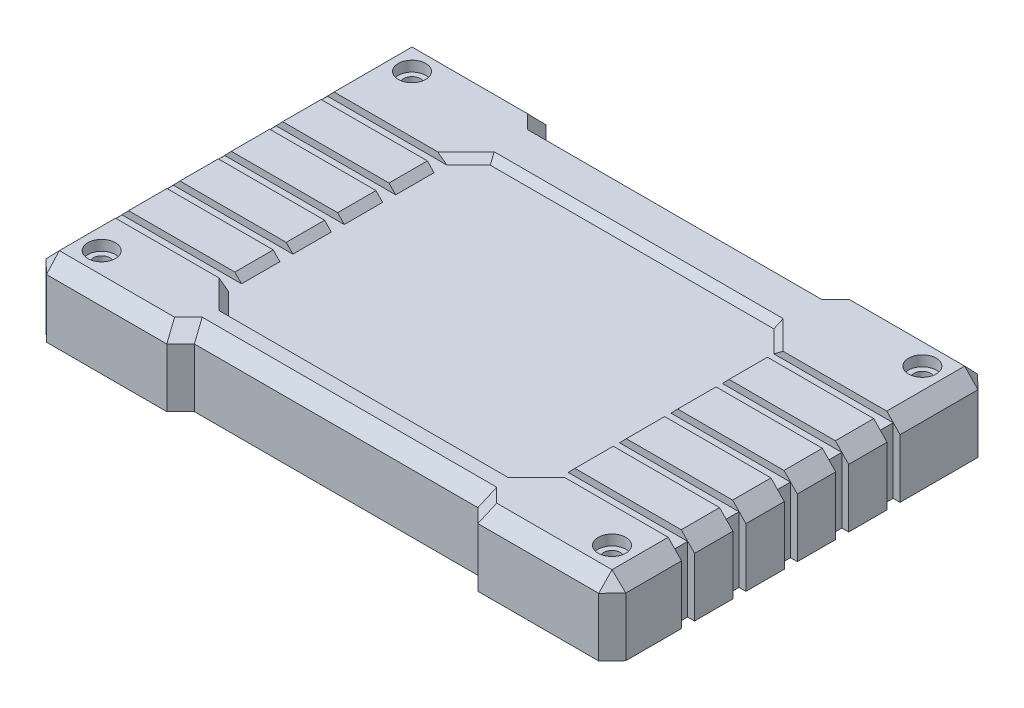
SolidWorks part; units mm, degrees
ref_plane "Спереди" through (0, 0, 0) normal (0, 0, 1) x (1, 0, 0)
ref_plane "Сверху" through (0, 0, 0) normal (0, 1, 0) x (1, 0, 0)
ref_plane "Справа" through (0, 0, 0) normal (1, 0, 0) x (0, 0, -1)
sketch "Эскиз1" plane through (0, 0, 0) normal (0, 1, 0) x (1, 0, 0)
  line L6 (-37, -22.5) -> (37, -22.5)
  line L9 (-37, -22.5) -> (-37, 22.5)
  line L14 (-37, 22.5) -> (37, 22.5)
  line L15 (37, -22.5) -> (37, 22.5)
  line L20 (-37, -22.5) -> (37, 22.5) construction
  line L21 (-37, 22.5) -> (37, -22.5) construction
  dimension "D1" = 74
  dimension "D2" = 45
extrude "Бобышка-Вытянуть1" add sketch "Эскиз1" along normal blind 2
sketch "Эскиз2" plane through (-37, 0, 0) normal (-1, 0, 0) x (0, 0, 1)
  line L0 (22.5, 2) -> (22.5, 0) construction
  line L1 (-22.5, 2) -> (22.5, 2)
  line L2 (-22.5, 2) -> (-22.5, -7.5)
  line L3 (-22.5, -7.5) -> (22.5, -7.5)
  line L4 (22.5, 2) -> (22.5, -7.5)
  dimension "D1" = 9.5
extrude "Бобышка-Вытянуть2" add sketch "Эскиз2" along normal blind 4
sketch "Эскиз3" plane through (37, 0, 0) normal (1, 0, 0) x (0, 0, -1)
  line L1 (-22.5, 2) -> (22.5, 2)
  line L2 (-22.5, 2) -> (-22.5, -7.5)
  line L3 (-22.5, -7.5) -> (22.5, -7.5)
  line L4 (22.5, 2) -> (22.5, -7.5)
extrude "Бобышка-Вытянуть3" add sketch "Эскиз3" along normal blind 4
sketch "Эскиз4" plane through (0, 0, -22.5) normal (0, 0, -1) x (-1, 0, 0)
  line L1 (-41, 2) -> (41, 2)
  line L2 (-41, 2) -> (-41, -7.5)
  line L3 (-41, -7.5) -> (41, -7.5)
  line L4 (41, 2) -> (41, -7.5)
extrude "Бобышка-Вытянуть4" add sketch "Эскиз4" along normal blind 3
sketch "Эскиз5" plane through (0, 0, 22.5) normal (0, 0, 1) x (1, 0, 0)
  line L1 (-41, 2) -> (41, 2)
  line L2 (-41, 2) -> (-41, -7.5)
  line L3 (-41, -7.5) -> (41, -7.5)
  line L4 (41, 2) -> (41, -7.5)
extrude "Бобышка-Вытянуть5" add sketch "Эскиз5" along normal blind 3
sketch "Эскиз13" plane through (0, 0, 0) normal (0, -1, 0) x (1, 0, 0)
  line L0 (0, 22.5) -> (0, 0) construction
  line L1 (-37, 22.5) -> (37, 22.5) construction
  line L2 (-37, 22.5) -> (-37, -22.5) construction
  line L3 (-37, -22.5) -> (37, -22.5) construction
  line L4 (37, 22.5) -> (37, -22.5) construction
  line L5 (0, -1.75) -> (0, 0) construction
  line L6 (-33, -18.5) -> (33, -18.5) construction
  line L7 (-33, -18.5) -> (-33, 15) construction
  line L8 (-33, 15) -> (33, 15) construction
  line L9 (33, -18.5) -> (33, 15) construction
  line L10 (-33, -18.5) -> (33, 15) construction
  line L11 (-33, 15) -> (33, -18.5) construction
  line L14 (-37, -19.5) -> (-37, -22.5)
  line L16 (-37, -22.5) -> (-34, -22.5)
  line L17 (-37, 22.5) -> (-34, 22.5)
  line L18 (-37, 22.5) -> (-37, 19.5)
  line L19 (37, -22.5) -> (34, -22.5)
  line L20 (37, -19.5) -> (37, -22.5)
  line L21 (37, 22.5) -> (34, 22.5)
  line L22 (37, 22.5) -> (37, 19.5)
  circle A0 centre (-33, -18.5) radius 1 construction
  circle A1 centre (-33, -18.5) radius 2 construction
  circle A2 centre (33, -18.5) radius 1 construction
  circle A3 centre (33, -18.5) radius 2 construction
  circle A4 centre (-33, 15) radius 1 construction
  circle A5 centre (-33, 15) radius 2 construction
  circle A6 centre (33, 15) radius 1 construction
  circle A7 centre (33, 15) radius 2 construction
  circle A10 centre (-37, -22.5) radius 1 construction
  circle A12 centre (-37, -22.5) radius 3 construction
  arc A13 (-37, -19.5) -> (-34, -22.5) centre (-37, -22.5) cw
  arc A15 (-34, 22.5) -> (-37, 19.5) centre (-37, 22.5) cw
  arc A16 (37, -19.5) -> (34, -22.5) centre (37, -22.5) ccw
  arc A17 (34, 22.5) -> (37, 19.5) centre (37, 22.5) ccw
  point P9 (0, -1.75)
  dimension "D4" = 2
  dimension "D5" = 4
  dimension "D6" = 6
  dimension "D7" = 2
  dimension "D8" = 1.75
  dimension "D1" = 4
  dimension "D2" = 33.5
  dimension "D3" = 66
extrude "Бобышка-Вытянуть11" add sketch "Эскиз13" along normal up to vertex (7.5 mm away) up to point (-37, -7.5, -22.5)
sketch "Эскиз15" plane through (0, -7.5, 0) normal (0, -1, 0) x (1, 0, 0)
  line L0 (-37, -19.5) -> (-37, -22.5) construction
  line L1 (-34, -22.5) -> (-37, -22.5) construction
  line L2 (-37, 19.5) -> (-37, 22.5) construction
  line L3 (-34, 22.5) -> (-37, 22.5) construction
  line L4 (0, 22.5) -> (0, -22.5) construction
  line L5 (-34, 22.5) -> (34, 22.5) construction
  line L6 (34, -22.5) -> (-34, -22.5) construction
  line L7 (34, -22.5) -> (37, -22.5) construction
  line L8 (37, -22.5) -> (37, -19.5) construction
  line L9 (34, 22.5) -> (37, 22.5) construction
  line L10 (37, 22.5) -> (37, 19.5) construction
  circle A0 centre (-37, -22.5) radius 1.2
  arc A1 (-37, 19.5) -> (-34, 22.5) centre (-37, 22.5) ccw construction
  circle A2 centre (-37, 22.5) radius 1.2
  circle A3 centre (37, -22.5) radius 1.2
  circle A4 centre (37, 22.5) radius 1.2
  dimension "D1" = 2.4
extrude "Вырез-Вытянуть1" cut sketch "Эскиз15" against normal through all
sketch "Эскиз16" plane through (0, 0, 0) normal (0, -1, 0) x (1, 0, 0)
  line L0 (-37, -5.5) -> (3, -5.5) construction
  line L1 (37, -19) -> (-37, -19) construction
  line L2 (37, -19) -> (37, 22.5) construction
  line L3 (37, 22.5) -> (-37, 22.5) construction
  line L4 (-37, -19) -> (-37, 22.5) construction
  line L5 (0, 1.75) -> (0, 3.5) construction
  line L6 (-33, -15) -> (33, -15) construction
  line L7 (-33, -15) -> (-33, 18.5) construction
  line L8 (-33, 18.5) -> (33, 18.5) construction
  line L9 (33, -15) -> (33, 18.5) construction
  line L10 (-33, -15) -> (33, 18.5) construction
  line L11 (-33, 18.5) -> (33, -15) construction
  line L12 (37, -19) -> (-37, 22.5) construction
  line L13 (37, 22.5) -> (-37, -19) construction
  line L14 (3, -5.5) -> (3, -19) construction
  line L15 (-37, 22.5) -> (-37, -5.5) construction
  line L16 (3, -19) -> (37, -19) construction
  line L18 (-34, 22.5) -> (34, 22.5) construction
  line L19 (-34, 22.5) -> (34, 22.5) construction
  line L20 (37, 19.5) -> (37, -19) construction
  circle A0 centre (-33, -15) radius 0.9 construction
  circle A1 centre (-33, -1.5) radius 0.9
  circle A2 centre (33, -15) radius 0.9
  circle A3 centre (7, -15) radius 0.9
  circle A4 centre (-33, 18.5) radius 0.9
  circle A5 centre (33, 18.5) radius 0.9
  arc A7 (34, 22.5) -> (37, 19.5) centre (37, 22.5) ccw construction
  arc A8 (34, 22.5) -> (37, 19.5) centre (37, 22.5) ccw construction
  circle A9 centre (-33, 18.5) radius 2
  circle A10 centre (33, 18.5) radius 2
  circle A11 centre (33, -15) radius 2
  circle A12 centre (7, -15) radius 2
  circle A13 centre (-33, -1.5) radius 2
  point P7 (0, 1.75)
  dimension "D9" = 1.8
  dimension "D10" = 4
  dimension "D11" = 26
  dimension "D1" = 33.5
  dimension "D2" = 66
  dimension "D3" = 1.75
  dimension "D4" = 74
  dimension "D5" = 41.5
  dimension "D6" = 28
  dimension "D7" = 40
  dimension "D8" = 20
extrude "Бобышка-Вытянуть12" add sketch "Эскиз16" along normal blind 4
sketch "Эскиз17" plane through (-41, 0, 0) normal (-1, 0, 0) x (0, 0, 1)
  line L0 (15.531, -7.5) -> (9.969, -7.5)
  line L1 (15.531, -7.5) -> (15.531, 2)
  line L2 (15.531, 2) -> (9.969, 2)
  line L3 (9.969, -7.5) -> (9.969, 2)
  line L4 (-14.269, -7.5) -> (-25.5, -7.5)
  line L5 (8.081, -7.5) -> (2.519, -7.5)
  line L6 (8.081, -7.5) -> (8.081, 2)
  line L7 (8.081, 2) -> (2.519, 2)
  line L8 (2.519, -7.5) -> (2.519, 2)
  line L9 (0.631, -7.5) -> (-4.931, -7.5)
  line L10 (0.631, -7.5) -> (0.631, 2)
  line L11 (0.631, 2) -> (-4.931, 2)
  line L12 (-4.931, -7.5) -> (-4.931, 2)
  line L13 (-6.819, -7.5) -> (-12.381, -7.5)
  line L14 (-6.819, -7.5) -> (-6.819, 2)
  line L15 (-6.819, 2) -> (-12.381, 2)
  line L16 (-12.381, -7.5) -> (-12.381, 2)
  line L17 (-14.269, -7.5) -> (-14.269, 2)
  line L18 (-25.5, -7.5) -> (-25.5, 2)
  line L19 (-14.269, 2) -> (-25.5, 2)
  line L20 (17.419, -7.5) -> (25.5, -7.5)
  line L21 (17.419, -7.5) -> (17.419, 2)
  line L22 (25.5, -7.5) -> (25.5, 2)
  line L23 (17.419, 2) -> (25.5, 2)
  line L24 (-14.269, -7.5) -> (-12.381, -7.5) construction
  line L25 (-6.819, -7.5) -> (-4.931, -7.5) construction
  line L26 (0.631, -7.5) -> (2.519, -7.5) construction
  line L27 (8.081, -7.5) -> (9.969, -7.5) construction
  line L28 (15.531, -7.5) -> (17.419, -7.5) construction
  line L29 (25.5, 2) -> (-25.5, 2) construction
  dimension "D1" = 8.081
  dimension "D2" = 11.231
  dimension "D3" = 5.562
  dimension "D4" = 1.888
extrude "Бобышка-Вытянуть13" add sketch "Эскиз17" along normal blind 1
sketch "Эскиз18" plane through (41, 0, 0) normal (1, 0, 0) x (0, 0, -1)
  line L0 (-15.531, 2) -> (-9.969, 2)
  line L1 (-15.531, 2) -> (-15.531, -7.5)
  line L2 (-15.531, -7.5) -> (-9.969, -7.5)
  line L3 (-9.969, 2) -> (-9.969, -7.5)
  line L4 (14.269, 2) -> (25.5, 2)
  line L5 (-8.081, 2) -> (-2.519, 2)
  line L6 (-8.081, 2) -> (-8.081, -7.5)
  line L7 (-8.081, -7.5) -> (-2.519, -7.5)
  line L8 (-2.519, 2) -> (-2.519, -7.5)
  line L9 (-0.631, 2) -> (4.931, 2)
  line L10 (-0.631, 2) -> (-0.631, -7.5)
  line L11 (-0.631, -7.5) -> (4.931, -7.5)
  line L12 (4.931, 2) -> (4.931, -7.5)
  line L13 (6.819, 2) -> (12.381, 2)
  line L14 (6.819, 2) -> (6.819, -7.5)
  line L15 (6.819, -7.5) -> (12.381, -7.5)
  line L16 (12.381, 2) -> (12.381, -7.5)
  line L17 (14.269, 2) -> (14.269, -7.5)
  line L18 (25.5, 2) -> (25.5, -7.5)
  line L19 (14.269, -7.5) -> (25.5, -7.5)
  line L20 (-17.419, 2) -> (-25.5, 2)
  line L21 (-17.419, 2) -> (-17.419, -7.5)
  line L22 (-25.5, 2) -> (-25.5, -7.5)
  line L23 (-17.419, -7.5) -> (-25.5, -7.5)
  line L24 (14.269, 2) -> (12.381, 2) construction
  line L25 (6.819, 2) -> (4.931, 2) construction
  line L26 (-0.631, 2) -> (-2.519, 2) construction
  line L27 (-8.081, 2) -> (-9.969, 2) construction
  line L28 (-15.531, 2) -> (-17.419, 2) construction
  line L30 (-25.5, -7.5) -> (25.5, -7.5) construction
  dimension "D1" = 8.081
  dimension "D2" = 11.231
  dimension "D3" = 5.562
  dimension "D4" = 1.888
extrude "Бобышка-Вытянуть14" add sketch "Эскиз18" along normal blind 1
sketch "Эскиз19" plane through (0, 2, 0) normal (0, 1, 0) x (1, 0, 0)
  line L0 (-42, 25.5) -> (-42, 27.5)
  line L1 (-42, -25.5) -> (-42, -27.5)
  line L2 (42, 25.5) -> (42, 27.5)
  line L3 (42, -25.5) -> (42, -27.5)
  line L4 (42, -27.5) -> (22.5537, -27.5)
  line L5 (-42, -27.5) -> (-22.5537, -27.5)
  line L6 (-42, 27.5) -> (-22.5537, 27.5)
  line L7 (42, 27.5) -> (22.5537, 27.5)
  line L8 (-22.5537, 17.6481) -> (-22.5537, 27.5) construction
  line L9 (-22.5537, 27.5) -> (-20.5537, 25.5)
  line L10 (-20.5537, 25.5) -> (-42, 25.5)
  line L11 (22.5537, 27.5) -> (20.5537, 25.5)
  line L12 (42, 25.5) -> (20.5537, 25.5)
  line L13 (-22.5537, -27.5) -> (-20.5537, -25.5)
  line L14 (-20.5537, -25.5) -> (-42, -25.5)
  line L15 (22.5537, -27.5) -> (20.5537, -25.5)
  line L16 (20.5537, -25.5) -> (42, -25.5)
  dimension "D1" = 2
  dimension "D2" = 45
  dimension "D3" = 45
  dimension "D4" = 45
  dimension "D5" = 45
extrude "Бобышка-Вытянуть15" add sketch "Эскиз19" against normal up to surface (9.5 mm away) up to face at (-37, -7.5, 21.3)
sketch "Эскиз20" plane through (0, 2, 0) normal (0, 1, 0) x (1, 0, 0)
  line L0 (-41, 14.269) -> (41, 14.269) construction
  line L1 (-41, 12.381) -> (41, 12.381) construction
  line L2 (41, 6.819) -> (-41, 6.819) construction
  line L3 (-41, 4.931) -> (41, 4.931) construction
  line L4 (41, -0.631) -> (-41, -0.631) construction
  line L5 (-41, -2.519) -> (41, -2.519) construction
  line L6 (-41, -8.081) -> (41, -8.081) construction
  line L7 (-41, -9.969) -> (41, -9.969) construction
  line L8 (41, -15.531) -> (-41, -15.531) construction
  line L9 (-41, -17.419) -> (41, -17.419) construction
  line L10 (23.6884, -17.419) -> (23.6884, 14.269) construction
  line L11 (-23.6884, 14.269) -> (-20.5537, 17.4037)
  line L12 (-20.5537, -25.5) -> (-20.5537, 25.5) construction
  line L13 (20.5537, -25.5) -> (20.5537, 25.5) construction
  line L14 (-20.5537, 25.5) -> (20.5537, -25.5) construction
  line L15 (20.5537, 25.5) -> (-20.5537, -25.5) construction
  line L16 (-20.5537, -20.5537) -> (-23.6884, -17.419)
  line L17 (20.5537, -20.5537) -> (-20.5537, -20.5537) construction
  line L18 (20.5537, -20.5537) -> (20.5537, 20.5537) construction
  line L19 (20.5537, 20.5537) -> (-20.5537, 20.5537) construction
  line L20 (-20.5537, -20.5537) -> (-20.5537, 20.5537) construction
  line L21 (20.5537, -20.5537) -> (-20.5537, 20.5537) construction
  line L22 (20.5537, 20.5537) -> (-20.5537, -20.5537) construction
  line L23 (20.5537, -20.5537) -> (23.6884, -17.419)
  line L24 (-20.5537, -20.5537) -> (20.5537, -20.5537)
  line L25 (-41, -17.419) -> (-23.6884, -17.419)
  line L26 (23.6884, -17.419) -> (41, -17.419)
  line L27 (-41, -17.419) -> (-42, -17.419)
  line L28 (-42, -17.419) -> (-42, -27.5)
  line L29 (-42, -27.5) -> (-22.5537, -27.5)
  line L30 (-22.5537, -27.5) -> (-20.5537, -25.5)
  line L31 (20.5537, -25.5) -> (22.5537, -27.5)
  line L32 (22.5537, -27.5) -> (42, -27.5)
  line L33 (42, -27.5) -> (42, -17.419)
  line L34 (42, -17.419) -> (41, -17.419)
  line L35 (-20.5537, -25.5) -> (20.5537, -25.5) construction
  line L36 (-23.6884, -17.419) -> (-23.6884, 14.269) construction
  line L37 (23.6884, 14.269) -> (20.5537, 17.4037)
  line L38 (-23.6884, 14.269) -> (-41, 14.269)
  line L39 (-41, 14.269) -> (-42, 14.269)
  line L40 (-42, 14.269) -> (-42, 27.5)
  line L41 (-42, 27.5) -> (-22.5537, 27.5)
  line L42 (-22.5537, 27.5) -> (-20.5537, 25.5)
  line L43 (-20.5537, 25.5) -> (20.5537, 25.5)
  line L44 (20.5537, 25.5) -> (22.5537, 27.5)
  line L45 (22.5537, 27.5) -> (42, 27.5)
  line L46 (42, 27.5) -> (42, 14.269)
  line L47 (42, 14.269) -> (41, 14.269)
  line L48 (41, 14.269) -> (23.6884, 14.269)
  line L49 (20.5537, 17.4037) -> (-20.5537, 17.4037)
  line L50 (-42, 12.381) -> (-23.6884, 12.381)
  line L51 (-23.6884, 12.381) -> (-23.6884, 6.819)
  line L52 (-23.6884, 6.819) -> (-42, 6.819)
  line L53 (-42, 6.819) -> (-42, 12.381)
  line L54 (-42, 4.931) -> (-23.6884, 4.931)
  line L55 (-23.6884, 4.931) -> (-23.6884, -0.631)
  line L56 (-23.6884, -0.631) -> (-42, -0.631)
  line L57 (-42, -0.631) -> (-42, 4.931)
  line L58 (-42, -2.519) -> (-23.6884, -2.519)
  line L59 (-23.6884, -2.519) -> (-23.6884, -8.081)
  line L60 (-23.6884, -8.081) -> (-42, -8.081)
  line L61 (-42, -8.081) -> (-42, -2.519)
  line L62 (-42, -9.969) -> (-23.6884, -9.969)
  line L63 (-23.6884, -9.969) -> (-23.6884, -15.531)
  line L64 (-23.6884, -15.531) -> (-42, -15.531)
  line L65 (-42, -15.531) -> (-42, -9.969)
  line L66 (23.6884, 12.381) -> (42, 12.381)
  line L67 (42, 12.381) -> (42, 6.819)
  line L68 (23.6884, 6.819) -> (23.6884, 12.381)
  line L69 (41, 6.819) -> (23.6884, 6.819)
  line L70 (42, 6.819) -> (41, 6.819)
  line L71 (23.6884, 4.931) -> (42, 4.931)
  line L72 (42, 4.931) -> (42, -0.631)
  line L73 (42, -0.631) -> (23.6884, -0.631)
  line L74 (23.6884, -0.631) -> (23.6884, 4.931)
  line L75 (23.6884, -2.519) -> (42, -2.519)
  line L76 (42, -2.519) -> (42, -8.081)
  line L77 (42, -8.081) -> (23.6884, -8.081)
  line L78 (23.6884, -8.081) -> (23.6884, -2.519)
  line L79 (23.6884, -9.969) -> (42, -9.969)
  line L80 (42, -9.969) -> (42, -15.531)
  line L81 (42, -15.531) -> (23.6884, -15.531)
  line L82 (23.6884, -15.531) -> (23.6884, -9.969)
  line L83 (-20.5537, -25.5) -> (20.5537, -25.5)
  point P42 (0, 0)
  dimension "D1" = 45
  dimension "D2" = 45
  dimension "D3" = 45
  dimension "D4" = 45
extrude "Бобышка-Вытянуть16" add sketch "Эскиз20" along normal blind 1
chamfer "Фаска1" distance 2 angle 44 26 edges at (-42, 3, -9.6) (-42, 3, -2.15) (-42, 3, 5.3) (-42, 3, 12.75) (-42, 3, 22.4595) (-42, -2.25, 27.5) (-32.2768, 3, 27.5) (-21.5537, 3, 26.5) (0, 3, 25.5) (21.5537, 3, 26.5) (42, -2.25, 27.5) (32.2768, 3, 27.5) (42, 3, 22.4595) (42, 3, 12.75) (42, 3, 5.3) (42, 3, -2.15) (42, 3, -9.6) (-42, -2.25, -27.5) (-42, 3, -20.8845) (-32.2768, 3, -27.5) (-21.5537, 3, -26.5) (0, 3, -25.5) (21.5537, 3, -26.5) (42, 3, -20.8845) (42, -2.25, -27.5) (32.2768, 3, -27.5) first distance on face at (-42, -2.25, -9.6) first distance on face at (-42, -2.25, -2.15) first distance on face at (-42, -2.25, 5.3) first distance on face at (-42, -2.25, 12.75) first distance on face at (-42, -2.25, 22.4595) first distance on face at (-32.2768, -2.25, 27.5) first distance on face at (-21.5537, -2.25, 26.5) first distance on face at (0, -2.25, 25.5) first distance on face at (21.5537, -2.25, 26.5) first distance on face at (42, -2.25, 22.4595) first distance on face at (32.2768, -2.25, 27.5) first distance on face at (42, -2.25, 12.75) first distance on face at (42, -2.25, 5.3) first distance on face at (42, -2.25, -2.15) first distance on face at (42, -2.25, -9.6) first distance on face at (-42, -2.25, -20.8845) first distance on face at (-32.2768, -2.25, -27.5) first distance on face at (-21.5537, -2.25, -26.5) first distance on face at (0, -2.25, -25.5) first distance on face at (21.5537, -2.25, -26.5) first distance on face at (42, -2.25, -20.8845) first distance on face at (32.2768, -2.25, -27.5)
chamfer "Фаска2" distance 1 angle 44 14 edges at (-23.6884, 3, 12.75) (-23.6884, 3, 5.3) (-23.6884, 3, -2.15) (-23.6884, 3, -9.6) (-22.1211, 3, -15.8363) (0, 3, -17.4037) (22.1211, 3, -15.8363) (23.6884, 3, -9.6) (23.6884, 3, -2.15) (23.6884, 3, 5.3) (23.6884, 3, 12.75) (-22.1211, 3, 18.9863) (22.1211, 3, 18.9863) (0, 3, 20.5537) first distance on face at (-23.6884, 2.5, 12.75) first distance on face at (-23.6884, 2.5, 5.3) first distance on face at (-23.6884, 2.5, -2.15) first distance on face at (-23.6884, 2.5, -9.6) first distance on face at (-22.1211, 2.5, -15.8363) first distance on face at (0, 2.5, -17.4037) first distance on face at (22.1211, 2.5, -15.8363) first distance on face at (23.6884, 2.5, -9.6) first distance on face at (23.6884, 2.5, -2.15) first distance on face at (23.6884, 2.5, 5.3) first distance on face at (23.6884, 2.5, 12.75) first distance on face at (-22.1211, 2.5, 18.9863) first distance on face at (22.1211, 2.5, 18.9863) first distance on face at (0, 2.5, 20.5537)
sketch "Эскиз22" plane through (-37, 0, 0) normal (1, 0, 0) x (0, 0, -1)
  line L0 (-19.5, 0) -> (-13.4, 0) construction
  line L1 (19.5, 0) -> (-19.5, 0) construction
  line L2 (-13.4, 0) -> (-13.4, -7.5) construction
  line L3 (19.5, -7.5) -> (-19.5, -7.5) construction
  circle A0 centre (-13.4, -7.5) radius 1.6
  dimension "D3" = 3.2
  dimension "D1" = 6.1
  dimension "D2" = 7.5
extrude "Вырез-Вытянуть3" cut sketch "Эскиз22" against normal up to surface (5 mm away) up to face at (-42, -3.25, 12.75)
sketch "Эскиз23" plane through (-37, 0, 0) normal (1, 0, 0) x (0, 0, -1)
  line L0 (-2.37, -7.5) -> (-10.37, -7.5) construction
  line L1 (-10.37, -7.5) -> (-10.37, -6.45) construction
  line L2 (-10.37, -6.45) -> (-9.12, -5.2) construction
  line L3 (-9.12, -5.2) -> (-3.62, -5.2) construction
  line L4 (-3.62, -5.2) -> (-2.37, -6.45) construction
  line L5 (-2.37, -6.45) -> (-2.37, -7.5) construction
  line L6 (19.5, -7.5) -> (-11.8, -7.5) construction
  line L7 (-2.27, -7.5) -> (-2.27, -6.4086)
  line L8 (-0.631, -7.5) -> (-2.519, -7.5) construction
  line L9 (-2.27, -6.4086) -> (-3.5786, -5.1)
  line L10 (-3.5786, -5.1) -> (-9.1614, -5.1)
  line L11 (-9.1614, -5.1) -> (-10.47, -6.4086)
  line L12 (-10.47, -6.4086) -> (-10.47, -7.5)
  line L13 (-9.969, -7.5) -> (-11.8, -7.5) construction
  line L14 (-2.27, -7.5) -> (-10.47, -7.5)
  point P6 (-6.37, -7.5)
  dimension "D1" = 9.13
  dimension "D2" = 8
  dimension "D3" = 5.5
  dimension "D4" = 1.05
  dimension "D5" = 45
  dimension "D6" = 45
  dimension "D7" = 0.1
  dimension "D8" = 0.1
  dimension "D9" = 0.1
  dimension "D10" = 0.1
  dimension "D11" = 0.1
extrude "Вырез-Вытянуть4" cut sketch "Эскиз23" against normal up to surface (5 mm away) up to face at (-42, -3.25, 5.3)
sketch "Эскиз25" plane through (0, 2, 0) normal (0, -1, 0) x (1, 0, 0)
  circle A0 centre (-37, 22.5) radius 1.2
  circle A1 centre (-37, -22.5) radius 1.2
  circle A2 centre (-37, -22.5) radius 1.2 construction
  circle A3 centre (-37, 22.5) radius 1.2 construction
  circle A4 centre (37, 22.5) radius 1.2
  circle A5 centre (37, -22.5) radius 1.2
  circle A6 centre (37, 22.5) radius 1.2 construction
  circle A7 centre (37, -22.5) radius 1.2 construction
extrude "Вырез-Вытянуть5" cut sketch "Эскиз25" against normal through all
sketch "Эскиз26" plane through (0, 3, 0) normal (0, 1, 0) x (1, 0, 0)
  circle A0 centre (-37, 22.5) radius 2
  circle A1 centre (-37, -22.5) radius 2
  circle A2 centre (37, 22.5) radius 2
  circle A3 centre (37, -22.5) radius 2
  circle A4 centre (-37, 22.5) radius 1.2 construction
  circle A5 centre (-37, -22.5) radius 1.2 construction
  circle A6 centre (37, -22.5) radius 1.2 construction
  circle A7 centre (37, 22.5) radius 1.2 construction
  dimension "D1" = 4
extrude "Вырез-Вытянуть6" cut sketch "Эскиз26" against normal blind 1.5
sketch "Эскиз28" plane through (-42, 0, 0) normal (-1, 0, 0) x (0, 0, 1)
  line L0 (0.631, -7.5) -> (0.631, -4.2)
  line L1 (0.631, -7.5) -> (0.631, 2) construction
  line L3 (1.631, -3.2) -> (16.419, -3.2)
  line L4 (17.419, 2) -> (17.419, -7.5) construction
  line L5 (0.631, -7.5) -> (17.419, -7.5)
  line L8 (17.419, -7.5) -> (17.419, -4.2)
  line L10 (17.419, 1) -> (17.419, -7.5) construction
  line L11 (-4.931, -7.5) -> (0.631, -7.5) construction
  line L12 (0.631, -4.2) -> (1.631, -3.2)
  line L13 (16.419, -3.2) -> (17.419, -4.2)
  line L14 (3.5786, -5.1) -> (8.081, -5.1) construction
  point P2 (0.631, -3.2)
  point P5 (17.419, -3.2)
  dimension "D1" = 1.9
extrude "Вырез-Вытянуть7" cut sketch "Эскиз28" against normal blind 2.5
chamfer "Фаска3" distance 1 angle 45 2 edges at (-42, -3.2, 12.75) (-42, -3.2, 5.3)
